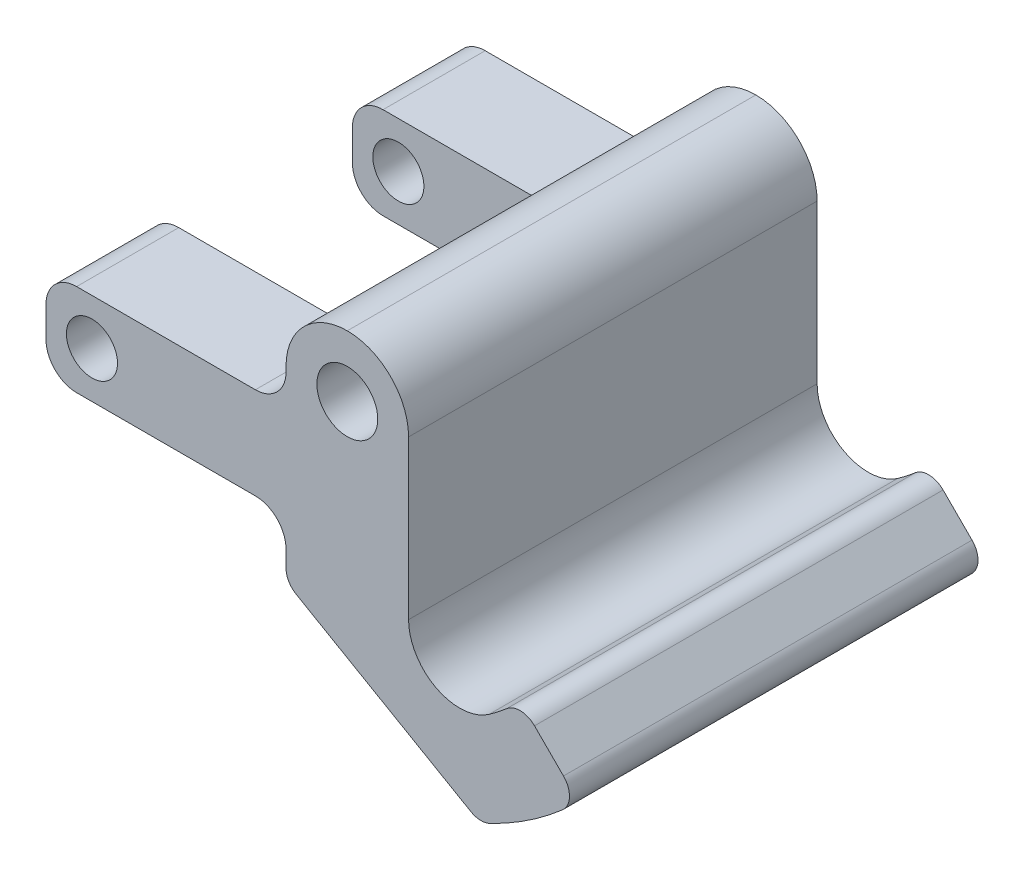
SolidWorks part; units mm, degrees
ref_plane "Front Plane" through (0, 0, 0) normal (0, 0, 1) x (1, 0, 0)
ref_plane "Top Plane" through (0, 0, 0) normal (0, 1, 0) x (1, 0, 0)
ref_plane "Right Plane" through (0, 0, 0) normal (1, 0, 0) x (0, 0, -1)
sketch "Sketch2" plane through (0, 0, 0) normal (0, 0, 1) x (1, 0, 0)
  line L1 (-6, 6) -> (6, 6)
  line L2 (-6, 6) -> (-6, -18.2707)
  line L4 (6, 6) -> (6, -23.2379)
  line L5 (16.9706, -16.9706) -> (22.6274, -22.6274)
  line L6 (0, 0) -> (16.9706, -16.9706) construction
  line L7 (0, -24) -> (0, 0) construction
  line L10 (-6, -18.2707) -> (13, -29.2404)
  arc A0 (6, -23.2379) -> (16.9706, -16.9706) centre (0, 0) ccw
  arc A1 (13, -29.2404) -> (22.6274, -22.6274) centre (0, 0) ccw
  circle A2 centre (0, 0) radius 2.98
  arc A3 (0, -24) -> (6, -23.2379) centre (0, 0) ccw construction
  point P10 (0, 0)
  point P13 (15.7864, -27.8351)
  point P14 (0, 0)
  point P15 (11.9027, -29.704)
  point P16 (-6, -24)
  point P17 (10, -30.3974)
  point P18 (0, 0)
  point P19 (-6, -18.4108)
  dimension "D2" = 5.96
  dimension "D5" = 24
  dimension "D1" = 6
  dimension "D3" = 12
  dimension "D4" = 45
  dimension "D6" = 8
  dimension "D7" = 13
  dimension "D8" = 60
extrude "Boss-Extrude1" add sketch "Sketch2" along normal mid plane 40
fillet "Fillet1" radius 6 2 edges at (6, 6, 0) (-6, 6, 0)
fillet "Fillet2" radius 2 4 edges at (22.6274, -22.6274, 0) (16.9706, -16.9706, 0) (-6, -18.2707, 0) (13, -29.2404, 0)
fillet "Fillet4" radius 5 1 edges at (6, -23.2379, 0)
sketch "Sketch3" plane through (0, 0, 20) normal (0, 0, 1) x (1, 0, 0)
  line L0 (-6, -3.5) -> (-29.5, -3.5)
  line L1 (-6, 0) -> (-6, -17.116) construction
  line L2 (-29.5, -3.5) -> (-29.5, -12.5)
  line L3 (-29.5, -12.5) -> (-6, -12.5)
  line L4 (-6, -12.5) -> (-6, -3.5)
  line L5 (-25, -8) -> (-29.5, -8) construction
  circle A0 centre (-25, -8) radius 2.5
  dimension "D1" = 5
  dimension "D3" = 8
  dimension "D4" = 9
  dimension "D5" = 25
  dimension "D2" = 4.5
extrude "Boss-Extrude2" add sketch "Sketch3" against normal blind 10
fillet "Fillet3" radius 3 4 edges at (-29.5, -12.5, 15) (-29.5, -3.5, 15) (-6, -12.5, 15) (-6, -3.5, 15)
mirror "Mirror1" about plane through (0, 0, 0) normal (0, 0, 1) of "Fillet3", "Boss-Extrude2"
equation "\"D4@Sketch2\"=70-25"
equation "\"D2@Sketch3\"=\"D4@Sketch3\"/2"
